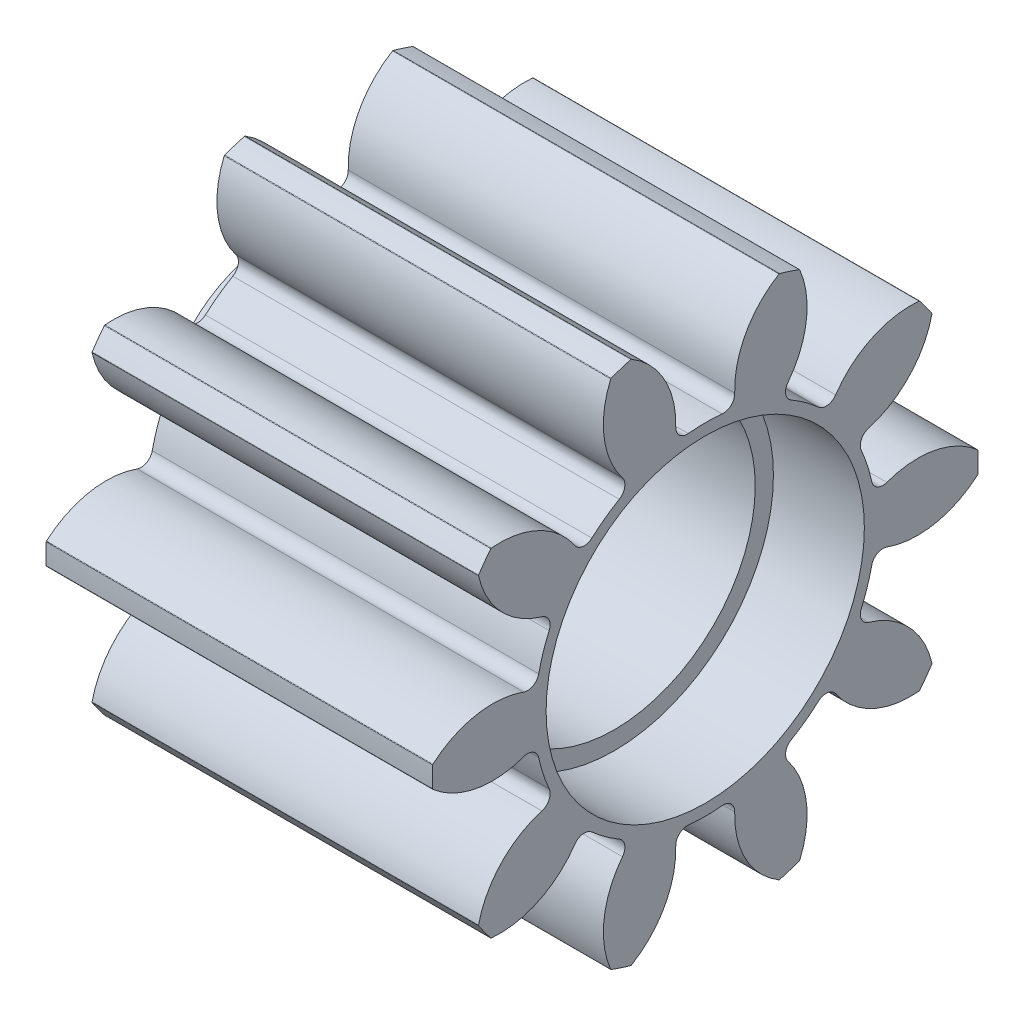
SolidWorks part; units mm, degrees
ref_plane "Plane1" through (0, 0, 0) normal (0, 0, 1) x (1, 0, 0)
ref_plane "Plane2" through (0, 0, 0) normal (0, 1, 0) x (1, 0, 0)
ref_plane "Plane3" through (0, 0, 0) normal (1, 0, 0) x (0, 0, -1)
sketch "HoldingSke" plane through (0, 0, 0) normal (0, 1, 0) x (1, 0, 0)
  line L0 (0, 0) -> (0.9848, -0.1736)
  line L1 (-15, 0) -> (100, 0) construction
  line L2 (0, 0) -> (-2.1039, 2.3779)
  line L3 (0, 0) -> (-11.863, 4.5341)
  line L4 (0, 0) -> (8.5048, 1.4996)
  line L5 (0, 0) -> (-46.8476, -17.4728)
  line L6 (0, 0) -> (-8.2896, -5.593)
  line L7 (-2.1039, 2.3779) -> (8.6586, 51.2059)
  line L8 (-76.2, 54.61) -> (-75.7, 54.61)
  line L9 (-67.7845, 28.3722) -> (-49.3413, 33.142)
  line L10 (-76.2, 71.12) -> (104.1128, 71.12)
  line L11 (0, 0) -> (-10, 0)
  line L12 (-76.2, 101.6) -> (-76.162, 101.6)
  line L13 (24.9733, 27.94) -> (52.9518, 28.4284)
  line L14 (24.9733, 27.94) -> (24.9743, 27.94)
  line L15 (24.9733, 27.94) -> (100.4006, 29.5858)
  line L16 (-63.627, -1) -> (-12.827, -1)
  circle A0 centre (0, 0) radius 1.5
  circle A1 centre (0, 0) radius 3.749
  circle A2 centre (0, 0) radius 37.5
  circle A3 centre (0, 0) radius 1.5
  dimension "Num_teeth" = 10
  dimension "Pitch_radius" = 180.3128
  dimension "Width" = 10
sketch "BasProSke" plane through (0, 0, 0) normal (0, 1, 0) x (1, 0, 0)
  line L0 (-10, 0) -> (60, 0) construction
  line L1 (0, 0) -> (0, 6)
  line L2 (0, 0) -> (8.5, 0)
  line L3 (8.5, 0) -> (8.5, 6)
  line L4 (8.5, 6) -> (0, 6)
  dimension "Thickness" = 8.5
  dimension "Diameter" = 12
revolve "Base-Revolve" add sketch "BasProSke" angle 360 about L0
sketch "TooCutSke" plane through (0, 0, 0) normal (1, 0, 0) x (0, 0, -1)
  line L1 (0, 0) -> (0, 107) construction
  line L2 (0, 0) -> (-0.8485, 4.9275) construction
  line L3 (0, 0) -> (-3.0584, 9.4126) construction
  line L4 (-0.8485, 4.9275) -> (-1.5292, 4.7063) construction
  arc A0 (0.6809, 3.6866) -> (-0.6809, 3.6866) centre (0, 0) ccw
  arc A1 (1.66, 5.7922) -> (-1.66, 5.7922) centre (0, 0) ccw
  circle A2 centre (0, 0) radius 5 construction
  circle A3 centre (0, 0) radius 4.8407 construction
  arc A4 (-0.6809, 3.6866) -> (-1.66, 5.7922) centre (-2.6471, 4.0528) ccw
  arc A5 (1.66, 5.7922) -> (0.6809, 3.6866) centre (2.6471, 4.0528) ccw
extrude "ToothCut" cut sketch "TooCutSke" along normal through all
fillet "Breaks" radius 0.02 2 edges at (4.25, 5.7745, -1.6294) (4.25, 5.7745, 1.6294) tangent propagation no
fillet "RootFillets" radius 0.251 2 edges at (4.25, 3.6866, -0.6809) (4.25, 3.6866, 0.6809)
pattern_circular "TeethCuts" count 10 every 36 about axis through (-10, 0, 0) along (1, 0, 0) of "ToothCut", "RootFillets", "Breaks"
sketch "HubNeaOneSke" plane through (0, 0, 0) normal (-1, 0, 0) x (0, 0, 1)
  circle A0 centre (0, 0) radius 3.749
  dimension "Diameter" = 7.498
extrude "HubNearOne" [suppressed] add sketch "HubNeaOneSke" along normal blind 41.5001
sketch "HubNeaBotSke" plane through (0, 0, 0) normal (-1, 0, 0) x (0, 0, 1)
  circle A0 centre (0, 0) radius 3.749
  dimension "Diameter" = 7.498
extrude "HubNearBoth" [suppressed] add sketch "HubNeaBotSke" along normal blind 20.75
ref_plane "FarPln" through (8.5, 0, 0) normal (1, 0, 0) x (0, 0, -1)
sketch "HubFarSke" plane through (8.5, 0, 0) normal (1, 0, 0) x (0, 0, -1)
  circle A0 centre (0, 0) radius 3.749
  dimension "Diameter" = 7.498
extrude "HubFar" [suppressed] add sketch "HubFarSke" along normal blind 20.75
sketch "BorSke" plane through (0, 0, 0) normal (1, 0, 0) x (0, 0, -1)
  circle A0 centre (0, 0) radius 1.8
  dimension "Diameter" = 3.6
extrude "Bore" cut sketch "BorSke" along normal mid plane 100.0001
sketch "KeySke" plane through (0, 0, 0) normal (1, 0, 0) x (0, 0, -1)
  line L0 (-0.6, 0) -> (-0.6, 2)
  line L1 (-0.6, 2) -> (0.6, 2)
  line L2 (0.6, 2) -> (0.6, 0)
  line L3 (0, 0) -> (0, 34) construction
  line L4 (-0.6, 0) -> (0.6, 0)
  dimension "Width" = 1.2
extrude "Keyway" [suppressed] cut sketch "KeySke" along normal mid plane 100.0001
pattern_circular "Keyway2" [suppressed] count 2 every 90 about axis through (-10, 0, 0) along (1, 0, 0) reverse direction yes
sketch "Sketch3" plane through (0, 0, 0) normal (-1, 0, 0) x (0, 0, 1)
  circle A0 centre (0, 0) radius 2.5
  circle A1 centre (0, 0) radius 1.8 construction
  circle A2 centre (0, 0) radius 1.8
  dimension "D1" = 5
extrude "Boss-Extrude1" add sketch "Sketch3" along normal blind 1
sketch "Sketch4" plane through (8.5, 0, 0) normal (1, 0, 0) x (0, 0, -1)
  circle A0 centre (0, 0) radius 3.5
  dimension "D1" = 7
extrude "Cut-Extrude2" cut sketch "Sketch4" against normal blind 2
sketch "Sketch5" plane through (6.5, 0, 0) normal (1, 0, 0) x (0, 0, -1)
  circle A0 centre (0, 0) radius 3.1
  dimension "D1" = 6.2
extrude "Cut-Extrude3" cut sketch "Sketch5" against normal blind 3
equation "' \"Module@HoldingSke\" = 6.35"
equation "' \"Num_teeth@HoldingSke\" = 12"
equation "' \"Ap@HoldingSke\" =  20"
equation "' \"Ap@HoldingSke\" = 20"
equation "' \"Width@HoldingSke\" = 0.5 * 25.4"
equation "' \"Hub_dia@HoldingSke\"= 1 * 25.4"
equation "' \"Hub_dia@HoldingSke\" = 1 * 25.4"
equation "' \"Overall_len@HoldingSke\" = 1.0 * 25.4"
equation "' \"Bore@HoldingSke\" = 0.75 * 25.4"
equation "' \"T_dim@HoldingSke\" = 0.1 * 25.4"
equation "' \"Width@KeySke\" = 0.25 * 25.4"
equation "' \"Show_teeth@HoldingSke\" = 13"
equation "' \"Backlash@HoldingSke\" = 0.009 * 25.4"
equation "' \"Addendum_fac@HoldingSke\" = 1.0"
equation "' \"Dedendum_fac@HoldingSke\" = 1.25"
equation "' \"Dedendum_add@HoldingSke\" = 0.00005 * 25.4"
equation "' \"Clearance_fac@HoldingSke\" = 0.25"
equation "\"Pitch@HoldingSke\" = 1 / \"Module@HoldingSke\""
equation "\"Overcut_dia@TooCutSke\" = (\"Num_teeth@HoldingSke\" + 2 * \"Addendum_fac@HoldingSke\") / \"Pitch@HoldingSke\" + 0.002 * 25.4"
equation "\"Pitch_dia@TooCutSke\" = \"Num_teeth@HoldingSke\" / \"Pitch@HoldingSke\""
equation "\"Base_dia@TooCutSke\" = \"Num_teeth@HoldingSke\" / \"Pitch@HoldingSke\" * cos((\"Ap@HoldingSke\"  * 3.14159265 / 180))"
equation "\"Root_dia@TooCutSke\" = (\"Num_teeth@HoldingSke\" + 2) / \"Pitch@HoldingSke\" - 2 * (\"Addendum_fac@HoldingSke\" + \"Dedendum_fac@HoldingSke\") / \"Pitch@HoldingSke\" - \"Dedendum_add@HoldingSke\" * 2"
equation "\"Half_ang@TooCutSke\" = 180 / \"Num_teeth@HoldingSke\""
equation "\"Half_CT@TooCutSke\" = \"Num_teeth@HoldingSke\" / \"Pitch@HoldingSke\" * sin((3.14159265 / 2 / \"Num_teeth@HoldingSke\")) / 2 - 7 * \"Backlash@HoldingSke\" / 4"
equation "\"Flank_rad@TooCutSke\" = \"Num_teeth@HoldingSke\" / \"Pitch@HoldingSke\" / 5"
equation "\"Radius@RootFillets\" = \"Clearance_fac@HoldingSke\" / \"Pitch@HoldingSke\" + \"Dedendum_add@HoldingSke\""
equation "\"Break_rad@Breaks\" = 0.02 / \"Pitch@HoldingSke\""
equation "\"Thickness@HoldingSke\" = \"Width@HoldingSke\""
equation "\"OAL@HoldingSke\" = \"Thickness@HoldingSke\""
equation "\"MHD@HoldingSke\" = (\"Num_teeth@HoldingSke\" + 2) / \"Pitch@HoldingSke\" - 2 * (\"Addendum_fac@HoldingSke\" + \"Dedendum_fac@HoldingSke\")  / \"Pitch@HoldingSke\" - \"Dedendum_add@HoldingSke\" * 2"
equation "\"MBD@HoldingSke\" = (\"Num_teeth@HoldingSke\" + 2) / \"Pitch@HoldingSke\" - 2 * (\"Addendum_fac@HoldingSke\" + \"Dedendum_fac@HoldingSke\")  / \"Pitch@HoldingSke\" - \"Dedendum_add@HoldingSke\" * 2 - 0.002 * 25.4"
equation "\"MHD@HoldingSke\" = ((sgn( \"MHD@HoldingSke\" - \"Hub_dia@HoldingSke\" )-1)*( \"MHD@HoldingSke\" - \"Hub_dia@HoldingSke\" ))/-2+ \"Hub_dia@HoldingSke\""
equation "\"MBD@HoldingSke\" = ((sgn( \"MBD@HoldingSke\" - \"Bore@HoldingSke\" )-1)*( \"MBD@HoldingSke\" - \"Bore@HoldingSke\" ))/-2+ \"Bore@HoldingSke\""
equation "\"OAL@HoldingSke\" = ((sgn( \"OAL@HoldingSke\" - \"Overall_len@HoldingSke\" )+1)*( \"OAL@HoldingSke\" - \"Overall_len@HoldingSke\" ))/2 + \"Overall_len@HoldingSke\" + 0.000002 * 25.4"
equation "\"Num_teeth@TeethCuts\" = int( \"Show_teeth@HoldingSke\" ) + 1"
equation "\"Num_teeth@TeethCuts\" = ((sgn( \"Num_teeth@TeethCuts\" - \"Num_teeth@HoldingSke\" )-1)*( \"Num_teeth@TeethCuts\" - \"Num_teeth@HoldingSke\" ))/-2+ \"Num_teeth@HoldingSke\""
equation "\"Num_teeth@TeethCuts\" = ((sgn( \"Num_teeth@TeethCuts\" - 2.0)+1)*( \"Num_teeth@TeethCuts\" - 2.0))/2 +2.0"
equation "\"Angle@TeethCuts\" = 360.0 / \"Num_teeth@HoldingSke\""
equation "\"Diameter@BasProSke\" = (\"Num_teeth@HoldingSke\" + 2 * \"Addendum_fac@HoldingSke\") / \"Pitch@HoldingSke\""
equation "' \"Fillet_rad@BasProSke\" =  \"Thickness@HoldingSke\" * 0.05"
equation "' \"Fillet_rad@BasProSke\" = \"Thickness@HoldingSke\" * 0.05"
equation "\"MHD@HoldingSke\" = ((sgn( \"MHD@HoldingSke\" - \"Root_dia@TooCutSke\" )-1)*( \"MHD@HoldingSke\" - \"Root_dia@TooCutSke\" ))/-2+ \"Root_dia@TooCutSke\""
equation "\"Diameter@HubNeaOneSke\" = \"MHD@HoldingSke\""
equation "\"Length@HubNearOne\" = \"OAL@HoldingSke\" - \"Thickness@BasProSke\""
equation "\"Diameter@HubNeaBotSke\" = \"MHD@HoldingSke\""
equation "\"Length@HubNearBoth\" = ( \"OAL@HoldingSke\" - \"Thickness@BasProSke\" ) / 2.0"
equation "\"Thickness@FarPln\" = \"Thickness@BasProSke\""
equation "\"Diameter@HubFarSke\" = \"MHD@HoldingSke\""
equation "\"Length@HubFar\" = ( \"OAL@HoldingSke\" - \"Thickness@BasProSke\" ) / 2.0"
equation "\"D1@Bore\" = \"OAL@HoldingSke\" * 2.0"
equation "\"D1@Keyway\" = \"OAL@HoldingSke\" * 2.0"
equation "\"Offset@KeySke\" = \"T_dim@HoldingSke\" + \"MBD@HoldingSke\" / 2.0"
